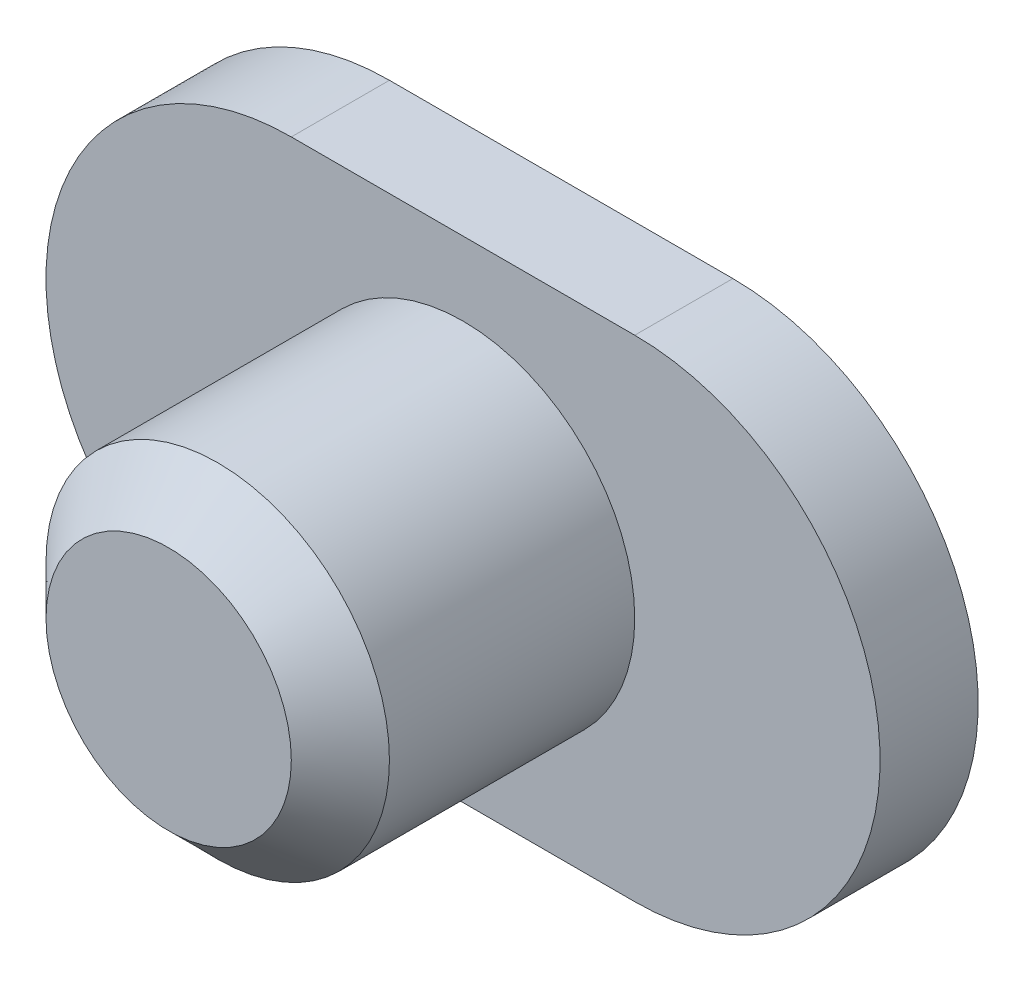
SolidWorks part; units mm, degrees
material "Латунь"
ref_plane "Спереди" through (0, 0, 0) normal (0, 0, 1) x (1, 0, 0)
ref_plane "Сверху" through (0, 0, 0) normal (0, 1, 0) x (1, 0, 0)
ref_plane "Справа" through (0, 0, 0) normal (1, 0, 0) x (0, 0, -1)
sketch "Эскиз1" plane through (0, 0, 0) normal (0, 0, 1) x (1, 0, 0)
  line L0 (-3.5, 0) -> (3.5, 0) construction
  line L1 (-3.5, 5) -> (3.5, 5)
  line L2 (-3.5, -5) -> (3.5, -5)
  arc A0 (-3.5, 5) -> (-3.5, -5) centre (-3.5, 0) ccw
  arc A1 (3.5, -5) -> (3.5, 5) centre (3.5, 0) ccw
  point P2 (0, 0)
  dimension "D1" = 5
  dimension "D2" = 7
extrude "Бобышка-Вытянуть1" add sketch "Эскиз1" along normal blind 2
sketch "Эскиз2" plane through (0, 0, 2) normal (0, 0, 1) x (1, 0, 0)
  circle A0 centre (0, 0) radius 3.5
  dimension "D1" = 7
extrude "Бобышка-Вытянуть2" add sketch "Эскиз2" along normal blind 6
sketch "Эскиз3" plane through (0, 0, 0) normal (0, 0, -1) x (-1, 0, 0)
  line L0 (0.75, 0) -> (-0.75, 0) construction
  line L1 (0.75, -2) -> (-0.75, -2)
  line L2 (0.75, 2) -> (-0.75, 2)
  arc A0 (0.75, -2) -> (0.75, 2) centre (0.75, 0) ccw
  arc A1 (-0.75, 2) -> (-0.75, -2) centre (-0.75, 0) ccw
  point P3 (0, 0)
  point P9 (0, 0)
  dimension "D1" = 4
  dimension "D2" = 1.5
extrude "Вырез-Вытянуть1" cut sketch "Эскиз3" against normal blind 4
chamfer "Фаска1" distance 1 angle 45 1 edges at (3.5, 0, 8)
ref_plane "Плоскость1" through (8.5, 0, 0) normal (1, 0, 0) x (0, 0, -1)
ref_plane "Плоскость2" through (3.5, 0, 0) normal (1, 0, 0) x (0, 0, -1)
ref_plane "Плоскость3" through (-3.5, 0, 0) normal (-1, 0, 0) x (0, 0, 1)
